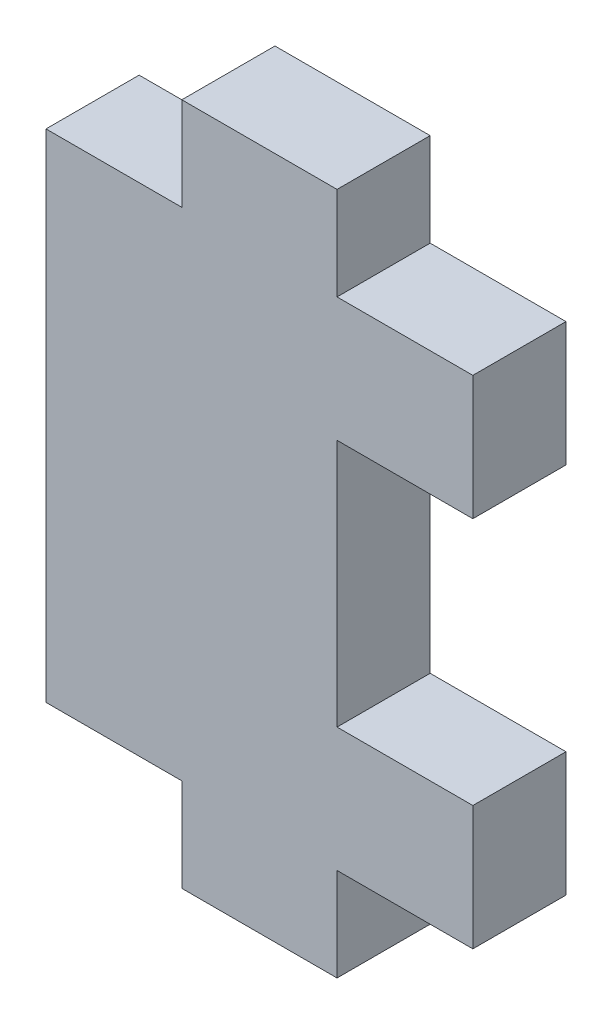
SolidWorks part; units mm, degrees
ref_plane "Plano frontal" through (0, 0, 0) normal (0, 0, 1) x (1, 0, 0)
ref_plane "Plano superior" through (0, 0, 0) normal (0, 1, 0) x (1, 0, 0)
ref_plane "Plano direito" through (0, 0, 0) normal (1, 0, 0) x (0, 0, -1)
sketch "Esboço1" plane through (0, 0, 0) normal (0, 0, 1) x (1, 0, 0)
  line L0 (0, 0) -> (13.75, 0) construction
  line L1 (-13.75, -16) -> (13.75, -16)
  line L2 (-13.75, -16) -> (-13.75, 16)
  line L3 (-13.75, 16) -> (13.75, 16)
  line L4 (13.75, -16) -> (13.75, 16)
  line L5 (-13.75, -16) -> (13.75, 16) construction
  line L6 (-13.75, 16) -> (13.75, -16) construction
  line L7 (5, 22) -> (-5, 22)
  line L8 (5, 22) -> (5, 16)
  line L9 (5, 16) -> (-5, 16)
  line L10 (-5, 22) -> (-5, 16)
  line L11 (5, 22) -> (-5, 16) construction
  line L12 (5, 16) -> (-5, 22) construction
  line L13 (5, -16) -> (-5, -16)
  line L14 (-5, -22) -> (-5, -16)
  line L15 (5, -22) -> (-5, -22)
  line L16 (5, -22) -> (5, -16)
  line L17 (5, -8) -> (5, 8)
  line L18 (5, 8) -> (13.75, 8)
  line L19 (5, -8) -> (13.75, -8)
  point P0 (0, 0)
  point P6 (0, 19)
  point P19 (5, 0)
  dimension "D1" = 6
  dimension "D2" = 10
  dimension "D3" = 32
  dimension "D4" = 27.5
  dimension "D5" = 8
extrude "Ressalto-extrusão1" add sketch "Esboço1" along normal blind 6 contours L1 L4 L3 L2 | L7 L10 L3 L8 | L15 L16 L1 L14 region at (-1.7736, 0, 0) region at (0, -19, 0) region at (0, 19, 0)
